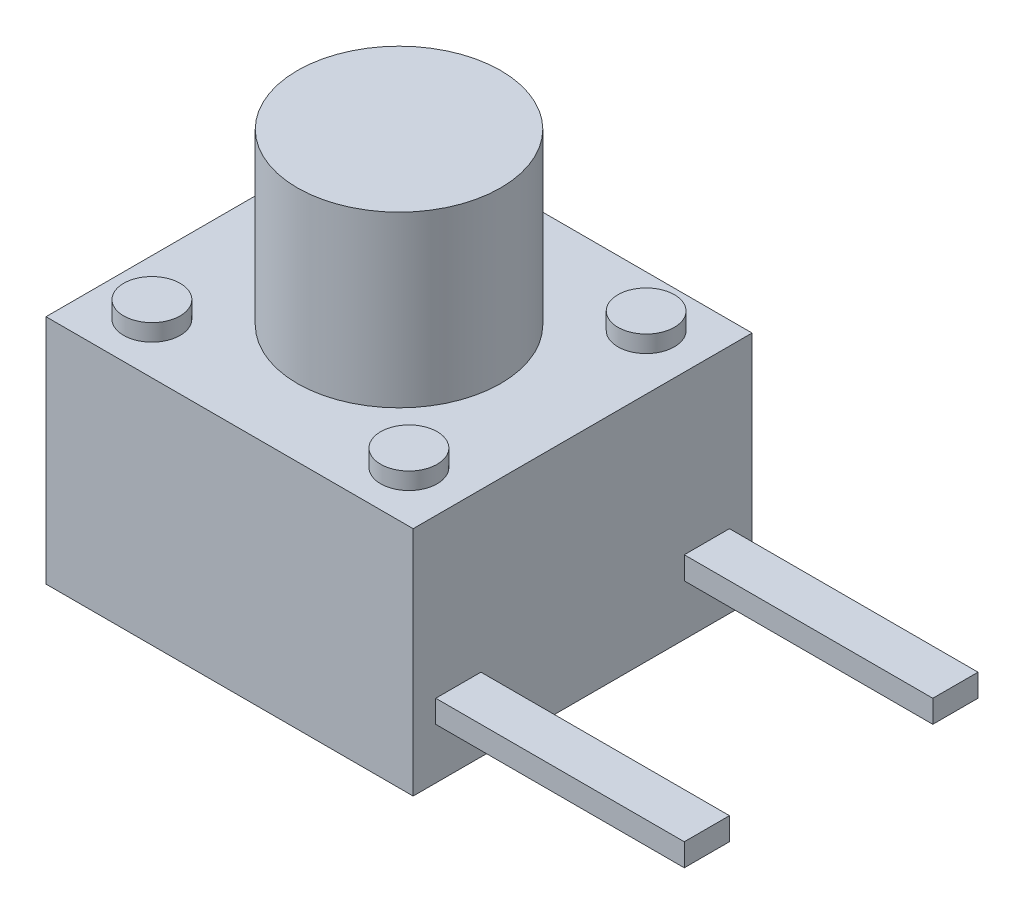
SolidWorks part; units mm, degrees
ref_plane "前视基准面" through (0, 0, 0) normal (0, 0, 1) x (1, 0, 0)
ref_plane "上视基准面" through (0, 0, 0) normal (0, 1, 0) x (1, 0, 0)
ref_plane "右视基准面" through (0, 0, 0) normal (1, 0, 0) x (0, 0, -1)
other "Configuration Table"
sketch "草图1" plane through (0, 0, 0) normal (0, 1, 0) x (1, 0, 0)
  line L1 (-3.25, -3) -> (3.25, -3)
  line L2 (-3.25, -3) -> (-3.25, 3)
  line L3 (-3.25, 3) -> (3.25, 3)
  line L4 (3.25, -3) -> (3.25, 3)
  line L5 (-3.25, -3) -> (3.25, 3) construction
  line L6 (-3.25, 3) -> (3.25, -3) construction
  circle A0 centre (0, 0) radius 1.8
  circle A1 centre (-2.275, 2.1) radius 0.5
  circle A2 centre (-2.275, -2.1) radius 0.5
  circle A3 centre (2.275, -2.1) radius 0.5
  circle A4 centre (2.275, 2.1) radius 0.5
  point P0 (0, 0)
  dimension "D3" = 3.6
  dimension "D5" = 1
  dimension "D1" = 6
  dimension "D2" = 6.5
  dimension "D4" = 4.2
extrude "凸台-拉伸1" add sketch "草图1" along normal blind 4.1 contours L3 L4 L1 L2
extrude "凸台-拉伸2" add sketch "草图1<3>" along normal blind 7.1 contours A0
sketch "草图1<3>" plane through (0, 0, 0) normal (0, 1, 0) x (1, 0, 0) same geometry as "草图1"
extrude "凸台-拉伸3" add sketch "草图1<4>" along normal blind 0.3 from surface contours A1 | A2 | A4 | A3 starting at face at (0, 4.1, -1.8)
sketch "草图1<4>" plane through (0, 0, 0) normal (0, 1, 0) x (1, 0, 0) same geometry as "草图1"
sketch "草图2" plane through (3.25, 0, 0) normal (1, 0, 0) x (0, 0, -1)
  line L0 (-1.8, 1.1) -> (1.8, 1.1)
  line L1 (-2.6, 0.9) -> (-1.8, 0.9)
  line L2 (-2.6, 0.9) -> (-2.6, 1.3)
  line L3 (-2.6, 1.3) -> (-1.8, 1.3)
  line L4 (-1.8, 0.9) -> (-1.8, 1.3)
  line L5 (1.8, 0.9) -> (2.6, 0.9)
  line L6 (1.8, 0.9) -> (1.8, 1.3)
  line L7 (1.8, 1.3) -> (2.6, 1.3)
  line L8 (2.6, 0.9) -> (2.6, 1.3)
  line L9 (0, 0) -> (0, 4.1)
  line L10 (-3, 4.1) -> (3, 4.1) construction
  line L12 (-3, 0) -> (3, 0) construction
  point P15 (0, 1.1)
  dimension "D1" = 5.2
  dimension "D2" = 0.8
  dimension "D3" = 0.4
  dimension "D4" = 1.3
extrude "凸台-拉伸4" add sketch "草图2" along normal blind 4.4 contours L3 L4 L1 L2 | L7 L8 L5 L6
